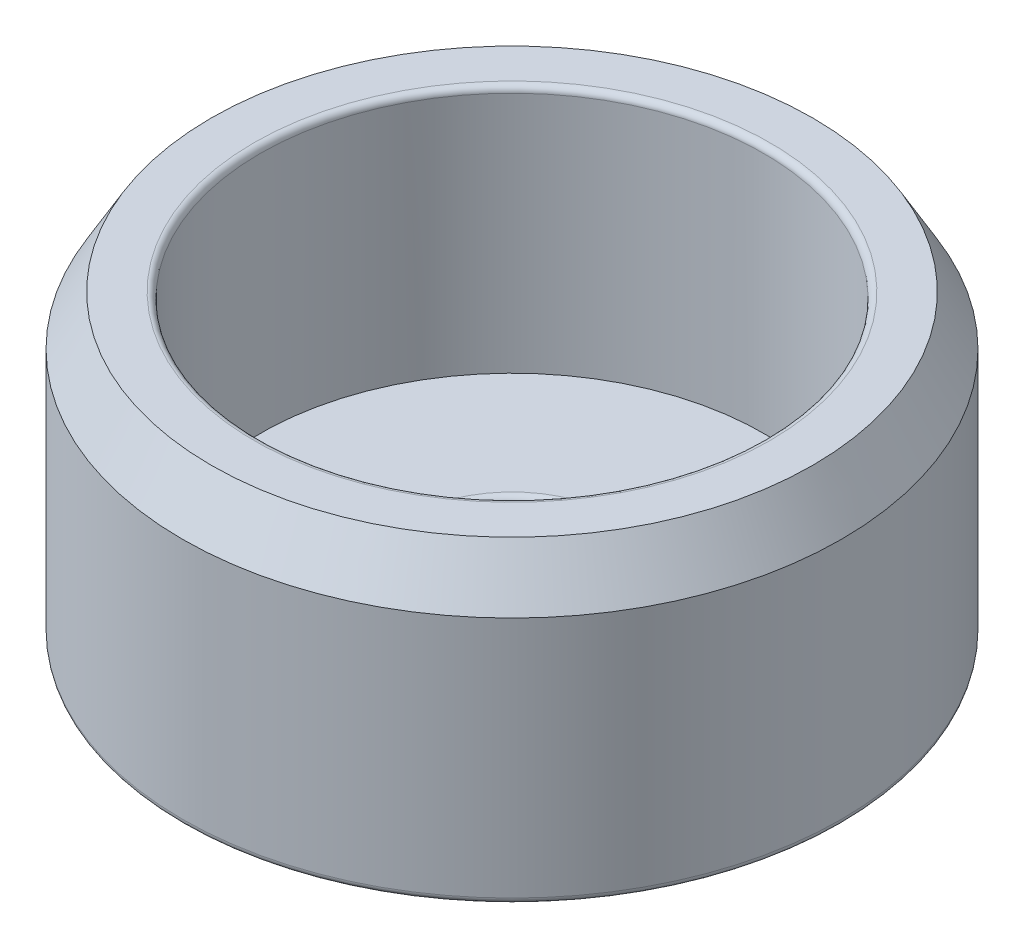
SolidWorks part; units mm, degrees
material "PET"
ref_plane "Front Plane" through (0, 0, 0) normal (0, 0, 1) x (1, 0, 0)
ref_plane "Top Plane" through (0, 0, 0) normal (0, 1, 0) x (1, 0, 0)
ref_plane "Right Plane" through (0, 0, 0) normal (1, 0, 0) x (0, 0, -1)
sketch "Sketch1" plane through (0, 0, 0) normal (0, 0, 1) x (1, 0, 0)
  line L0 (0, 0) -> (0, 12.4053) construction
  line L1 (20, 0) -> (15.3812, 8)
  line L2 (15.3812, 8) -> (40.5, 8)
  line L3 (40.5, 8) -> (40.5, 48)
  line L4 (40.5, 48) -> (48.3812, 48)
  line L5 (48.3812, 48) -> (53, 40)
  line L6 (53, 40) -> (53, 0)
  line L7 (53, 0) -> (20, 0)
  point P5 (0, 0)
  dimension "D1" = 40
  dimension "D2" = 60
  dimension "D3" = 81
  dimension "D4" = 106
  dimension "D5" = 8
  dimension "D6" = 30
  dimension "D7" = 40
  dimension "D8" = 8
revolve "body" add sketch "Sketch1" angle 360 about L0
fillet "overall_fillets" radius 1 4 edges at (15.3812, 8, 0) (20, 0, 0) (40.5, 48, 0) (53, 0, 0)
sketch "screw_hole_pos" plane through (0, 0, 0) normal (0, -1, 0) x (1, 0, 0)
  point P0 (43, 0)
  dimension "D1" = 43
hole_wizard "screw_holes" positions "screw_hole_pos" profile "Sketch4" hole size "Ø2.7" standard "DIN"
sketch "Sketch4" plane through (43, 0, 0) normal (1, 0, 0) x (0, 0, -1)
  line L0 (0, 0) -> (0, 6.8112)
  line L1 (0, 6.8112) -> (1.35, 6)
  line L2 (1.35, 6) -> (1.35, 0.4)
  line L3 (1.35, 0.4) -> (1.75, 0)
  line L5 (1.75, 0) -> (0, 0)
  line L6 (-1.35, 0.4) -> (-1.75, 0) construction
  line L10 (0, 6.8112) -> (-1.35, 6) construction
  line L11 (0, -6.35) -> (0, 107.95) construction
  dimension "Hole Dia." = 2.7
  dimension "Hole Depth" = 6
  dimension "Near C'Sink Dia." = 3.5
  dimension "Near C'Sink Angle" = 90
  dimension "Drill Angle" = 118
pattern_circular "CirPattern1" count 6 over 360 about axis through (0, 6.5, 0) along (0, 1, 0) of "screw_holes"
equation "\"paper_size\" = 600mm"
equation "\"cb_roll_d_outer\" = 80mm"
equation "\"cb_roll_d_inner\" = 78mm"
equation "\"attached_len\" = 70mm"
equation "\"helper_d\" = 86mm"
equation "\"outer_d\" = 106mm"
equation "\"spring_l_max\" = 25mm"
equation "\"spring_l_min\" = 10mm"
equation "\"cone_d_larger\" = 40mm"
equation "\"cone_angle\" = 60deg"
equation "\"D2@Sketch1\"=\"cone_angle\""
equation "\"D4@Sketch1\"=\"outer_d\""
equation "\"D3@Sketch1\"=\"cb_roll_d_outer\" + 1"
equation "\"D1@Sketch1\"=\"cone_d_larger\""
equation "\"bottom_screw_ring_d\" = 86mm"
equation "\"D1@screw_hole_pos\"=\"bottom_screw_ring_d\" / 2"
